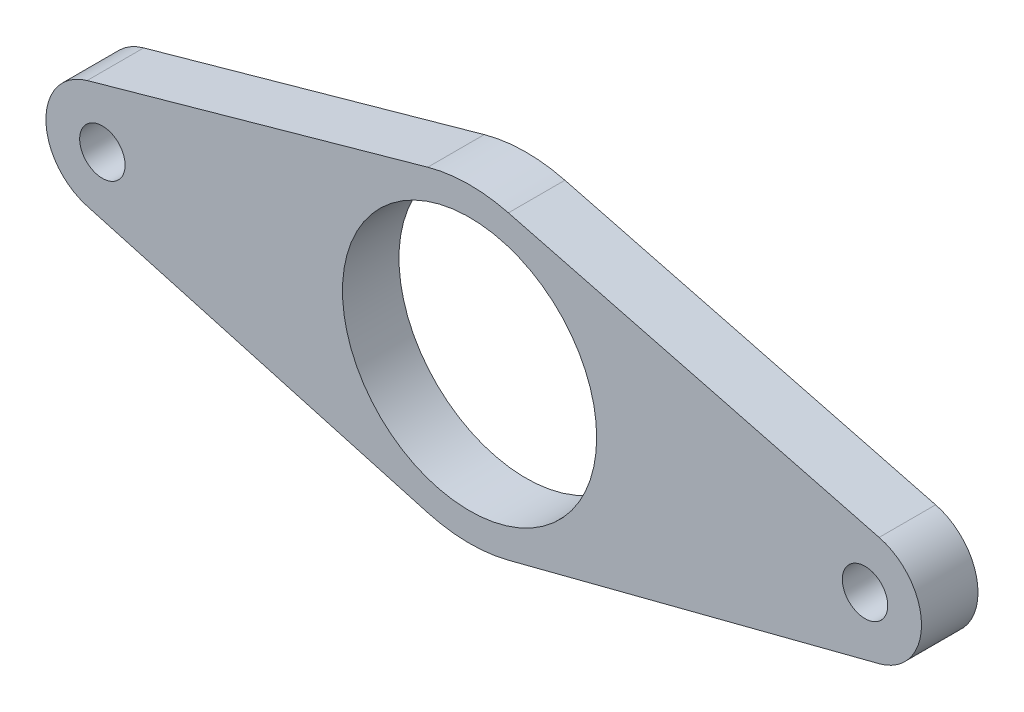
SolidWorks part; units mm, degrees
material "6061-T6 (SS)"
ref_plane "Front Plane" through (0, 0, 0) normal (0, 0, 1) x (1, 0, 0)
ref_plane "Top Plane" through (0, 0, 0) normal (0, 1, 0) x (1, 0, 0)
ref_plane "Right Plane" through (0, 0, 0) normal (1, 0, 0) x (0, 0, -1)
sketch "Sketch1" plane through (0, 0, 0) normal (0, 0, 1) x (1, 0, 0)
  line L0 (-42.9846, 6.1155) -> (-4.7014, 16.8177)
  line L1 (-42.9846, -6.1155) -> (-4.7014, -16.8177)
  line L2 (46.0375, -6.1484) -> (4.3656, -16.908)
  line L3 (46.0375, 6.1484) -> (4.3656, 16.908)
  arc A0 (-4.7014, -16.8177) -> (4.3656, -16.908) centre (0, 0) ccw
  circle A1 centre (-41.275, 0) radius 2.5527
  circle A2 centre (44.45, 0) radius 2.5527
  circle A3 centre (0, 0) radius 14.2875
  arc A4 (-42.9846, 6.1155) -> (-42.9846, -6.1155) centre (-41.275, 0) ccw
  arc A5 (46.0375, 6.1484) -> (46.0375, -6.1484) centre (44.45, 0) cw
  arc A6 (4.3656, 16.908) -> (-4.7014, 16.8177) centre (0, 0) ccw
  dimension "D1" = 28.575
  dimension "D2" = 5.1054
  dimension "D3" = 34.925
  dimension ".25" = 6.35
  dimension "D4" = 41.275
  dimension "D5" = 44.45
extrude "Boss-Extrude1" add sketch "Sketch1" along normal blind 6.35 contours L3 A6 L0 A4 L1 A0 L2 A5 A1 A2 A3 region at (-23.5619, 10.4608, 0)
